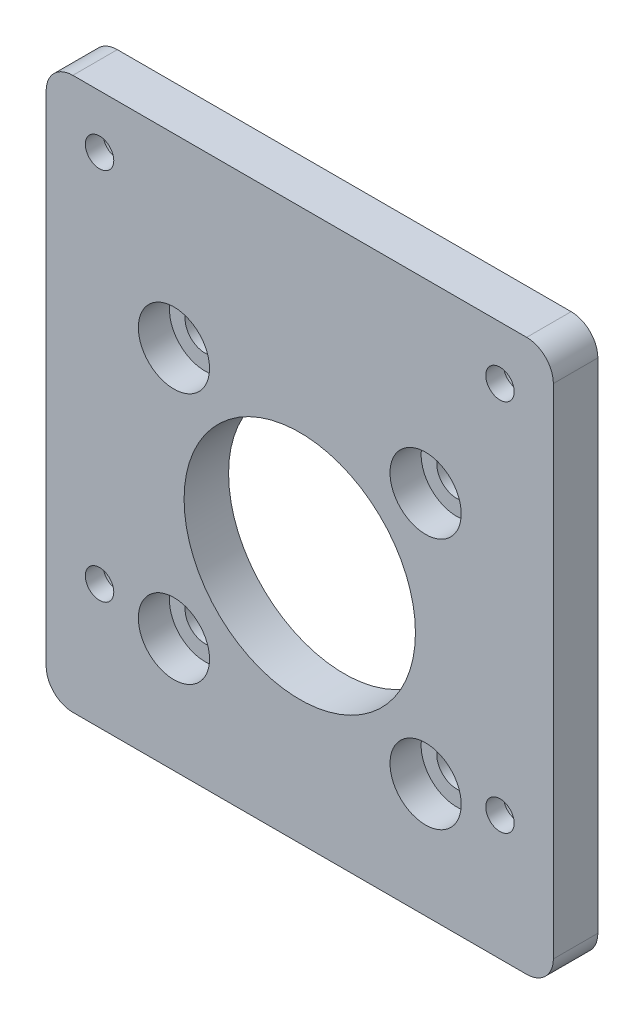
SolidWorks part; units mm, degrees
ref_plane "Front Plane" through (0, 0, 0) normal (0, 0, 1) x (1, 0, 0)
ref_plane "Top Plane" through (0, 0, 0) normal (0, 1, 0) x (1, 0, 0)
ref_plane "Right Plane" through (0, 0, 0) normal (1, 0, 0) x (0, 0, -1)
sketch "Sketch1" plane through (0, 0, 0) normal (0, 0, 1) x (1, 0, 0)
  line L0 (-191.1472, 63.5942) -> (-189.0259, 61.4729) construction
  line L5 (-141.0259, 16.4729) -> (-192.0259, 64.4729) construction
  line L6 (-141.0259, 64.4729) -> (-190.0961, 18.2835) construction
  line L7 (-166.5259, -50) -> (-166.5259, 130.9458) construction
  line L8 (-116.5259, 40.4729) -> (-216.5259, 40.4729) construction
  line L9 (-166.5259, 64.4729) -> (-166.5259, 32.4729) construction
  line L10 (-166.5259, 32.4729) -> (-176.3927, 40.9374) construction
  line L15 (-176.3927, 40.9374) -> (-156.6592, 24.0084) construction
  line L16 (-192.0259, 67.4729) -> (-141.0259, 67.4729)
  line L17 (-195.0259, 64.4729) -> (-195.0259, 8.4729)
  line L18 (-192.0259, 5.4729) -> (-141.0259, 5.4729)
  line L19 (-138.0259, 64.4729) -> (-138.0259, 8.4729)
  line L20 (-156.6592, 24.0084) -> (-166.5259, 32.4729)
  line L21 (-166.5259, 32.4729) -> (-157.3335, 41.6653)
  line L22 (-157.3335, 41.6653) -> (-175.7183, 23.2805) construction
  line L23 (-175.7183, 23.2805) -> (-180.668, 18.3308)
  arc A2 (-141.0259, 61.4729) -> (-141.9313, 63.6206) centre (-144.0259, 61.4729) ccw
  arc A3 (-189.0259, 64.4729) -> (-192.0259, 61.4729) centre (-189.0259, 61.4729) ccw
  circle A4 centre (-189.0259, 61.4729) radius 1.6
  circle A5 centre (-189.0259, 19.4729) radius 1.6
  circle A6 centre (-144.0259, 19.4729) radius 1.6
  circle A7 centre (-144.0259, 61.4729) radius 1.6
  circle A17 centre (-166.5259, 52.4729) radius 2.25 construction
  circle A19 centre (-166.5259, 32.4729) radius 13
  circle A20 centre (-186.5259, 32.4729) radius 2.25 construction
  circle A21 centre (-146.5259, 32.4729) radius 2.25 construction
  circle A22 centre (-166.5259, 12.4729) radius 2.25 construction
  circle A25 centre (-189.0259, 61.4729) radius 3
  circle A26 centre (-144.0259, 61.4729) radius 3
  circle A27 centre (-189.0259, 19.4729) radius 3
  circle A28 centre (-144.0259, 19.4729) radius 3
  arc A30 (-192.0259, 5.4729) -> (-195.0259, 8.4729) centre (-192.0259, 8.4729) cw
  arc A31 (-141.0259, 5.4729) -> (-138.0259, 8.4729) centre (-141.0259, 8.4729) ccw
  arc A32 (-138.0259, 64.4729) -> (-141.0259, 67.4729) centre (-141.0259, 64.4729) ccw
  arc A33 (-192.0259, 67.4729) -> (-195.0259, 64.4729) centre (-192.0259, 64.4729) ccw
  circle A34 centre (-180.668, 18.3308) radius 2.25
  circle A35 centre (-180.668, 46.615) radius 2.25
  circle A36 centre (-152.3838, 46.615) radius 2.25
  circle A37 centre (-152.3838, 18.3308) radius 2.25
  point P1 (-166.5243, 40.4714)
  point P23 (-166.5259, 40.4729)
  point P26 (-166.5259, 40.4729)
  point P32 (-166.5259, 67.4729)
  point P33 (-138.0259, 36.4729)
  point P34 (-166.5259, 36.5721)
  point P44 (-138.0259, 5.4729)
  point P51 (-138.0259, 67.4729)
  point P59 (-195.0259, 67.4729)
  point P73 (-166.5259, 32.4729)
  dimension "D3" = 57
  dimension "D4" = 32
  dimension "D6" = 62
  dimension "D7" = 3
  dimension "D8" = 26
  dimension "D10" = 4
  dimension "D1" = 51
  dimension "D2" = 48
  dimension "D5" = 0
  dimension "D9" = 7
extrude "Boss-Extrude1" add sketch "Sketch1" along normal blind 5 contours L19 L16 L17 L18 A28 A27 A26 A2 A25 A3 A22 A21 A20 A19 A17 | A2 A26 A7 | A3 A25 A4 | A27 A5 | A28 A6 region at (-166.5259, 66.6307, 0) region at (-146.7121, 60.3405, 0) region at (-186.9646, 63.5342, 0) region at (-191.9411, 19.4729, 0) region at (-146.9411, 19.4729, 0)
extrude "Cut-Extrude1" cut sketch "Sketch1<5>" along normal blind 3 contours A3 A25 A4 | A2 A26 A7 | A28 A6 | A27 A5 | A5 region at (-146.7121, 60.3405, 0) region at (-186.9646, 63.5342, 0) region at (-191.9411, 19.4729, 0) region at (-146.9411, 19.4729, 0)
sketch "Sketch1<5>" plane through (0, 0, 0) normal (0, 0, 1) x (1, 0, 0) same geometry as "Sketch1"
sketch "Sketch2" plane through (0, 0, 5) normal (0, 0, 1) x (1, 0, 0)
  circle A4 centre (-180.668, 46.615) radius 4
  circle A5 centre (-152.3838, 46.615) radius 4
  circle A6 centre (-152.3838, 18.3308) radius 4
  circle A7 centre (-180.668, 18.3308) radius 4
extrude "Cut-Extrude2" cut sketch "Sketch2" against normal blind 3.5
